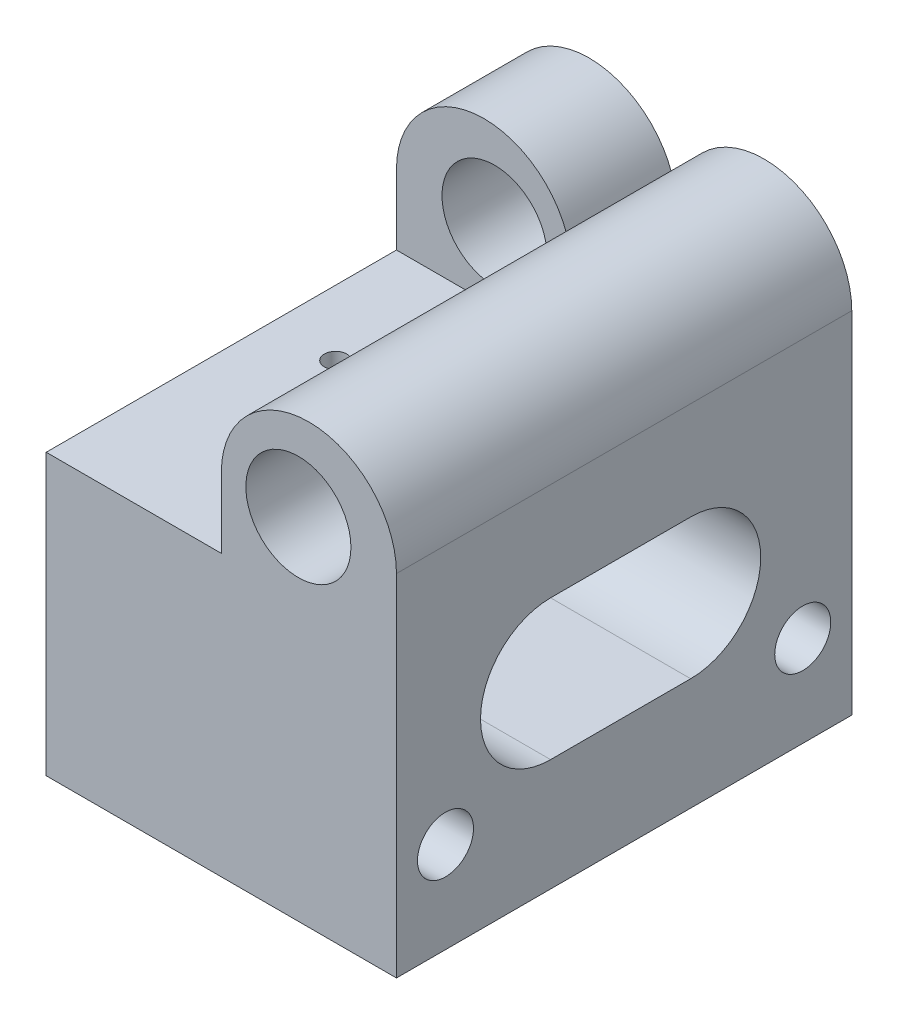
SolidWorks part; units mm, degrees
material "ABS"
ref_plane "Front Plane" through (0, 0, 0) normal (0, 0, 1) x (1, 0, 0)
ref_plane "Top Plane" through (0, 0, 0) normal (0, 1, 0) x (1, 0, 0)
ref_plane "Right Plane" through (0, 0, 0) normal (1, 0, 0) x (0, 0, -1)
sketch "Sketch1" plane through (0, 0, 0) normal (0, 0, 1) x (1, 0, 0)
  line L0 (0, 0) -> (50, 0)
  line L1 (50, 0) -> (50, 50)
  line L2 (0, 50) -> (0, 0)
  arc A0 (50, 50) -> (25, 58.6603) centre (36, 50) ccw
  arc A1 (25, 58.6603) -> (0, 50) centre (14, 50) ccw
  circle A2 centre (36, 50) radius 7.5
  circle A3 centre (14, 50) radius 7.5
  dimension "D2" = 22
  dimension "D5" = 15
  dimension "D1" = 50
  dimension "D4" = 50
extrude "Boss-Extrude1" add sketch "Sketch1" along normal blind 15
sketch "Sketch2" plane through (0, 0, 15) normal (0, 0, 1) x (1, 0, 0)
  line L0 (0, 0) -> (0, 50)
  line L4 (25, 50) -> (25, 0)
  line L5 (25, 0) -> (0, 0)
  line L6 (25, 0) -> (50, 0)
  line L7 (50, 0) -> (50, 50)
  line L8 (0, 0) -> (25, 0)
  circle A1 centre (14, 50) radius 7.5
  circle A2 centre (36, 50) radius 7.5 construction
  circle A3 centre (14, 50) radius 7.5 construction
  arc A4 (0, 50) -> (25, 50) centre (12.5, 50) cw
  arc A5 (50, 50) -> (25, 50) centre (37.5, 50) ccw
  line M7 (0, 0) -> (50, 0)
  line M8 (50, 0) -> (50, 50)
  arc M9 (50, 50) -> (25, 58.6603) centre (36, 50) ccw
  arc M10 (25, 58.6603) -> (0, 50) centre (14, 50) ccw
  circle M11 centre (36, 50) radius 7.5
extrude "Boss-Extrude2" add sketch "Sketch2" along normal blind 50 contours A5 L4 M8 M7 M11 region at (37.701, 27.2902, 15)
sketch "Sketch3" plane through (0, 0, 0) normal (0, 0, -1) x (-1, 0, 0)
  line L0 (0, 50) -> (0, 0) construction
  line L1 (-50, 0) -> (0, 0)
  line L2 (-50, 0) -> (-50, 40)
  line L3 (-50, 40) -> (0, 40)
  line L4 (0, 0) -> (0, 40)
  dimension "D1" = 40
extrude "Boss-Extrude3" add sketch "Sketch3" against normal blind 65
sketch "Sketch4" plane through (0, 0, 0) normal (-1, 0, 0) x (0, 0, 1)
  line L0 (23, 26) -> (43, 26) construction
  line L7 (23, 36) -> (43, 36)
  line L8 (23, 16) -> (43, 16)
  line L9 (65, 0) -> (65, 40) construction
  line L10 (65, 0) -> (0, 0) construction
  arc A2 (23, 36) -> (23, 16) centre (23, 26) ccw
  arc A3 (43, 16) -> (43, 36) centre (43, 26) ccw
  point P2 (33, 26)
  point P11 (32.5, 0)
  dimension "D2" = 10
  dimension "D4" = 20
  dimension "D1" = 22
  dimension "D3" = 16
extrude "Cut-Extrude1" cut sketch "Sketch4" against normal through all
extrude "Cut-Extrude2" cut sketch "Sketch2<3>" against normal through all contours A5 A4 M9 M10 region at (9.5874, 62.7381, 15)
sketch "Sketch2<3>" plane through (0, 0, 15) normal (0, 0, 1) x (1, 0, 0) same geometry as "Sketch2"
sketch "Sketch9" plane through (0, 0, 0) normal (-1, 0, 0) x (0, 0, 1)
  line L0 (0, 50) -> (0, 0) construction
  line L2 (65, 0) -> (65, 40) construction
  circle A1 centre (7, 13) radius 4
  arc A2 (23, 36) -> (23, 16) centre (23, 26) ccw construction
  circle A3 centre (58, 13) radius 4
  dimension "D1" = 8
  dimension "D2" = 13
  dimension "D3" = 7
  dimension "D4" = 7
extrude "Cut-Extrude3" cut sketch "Sketch9" against normal through all
sketch "Sketch10" plane through (0, 16, 0) normal (0, 1, 0) x (1, 0, 0)
  line L0 (50, -23) -> (0, -23) construction
  circle A0 centre (9.3061, -33) radius 1.6
  dimension "D1" = 3.2
  dimension "D2" = 10
extrude "Cut-Extrude4" cut sketch "Sketch10" along normal through all and the other way through all
